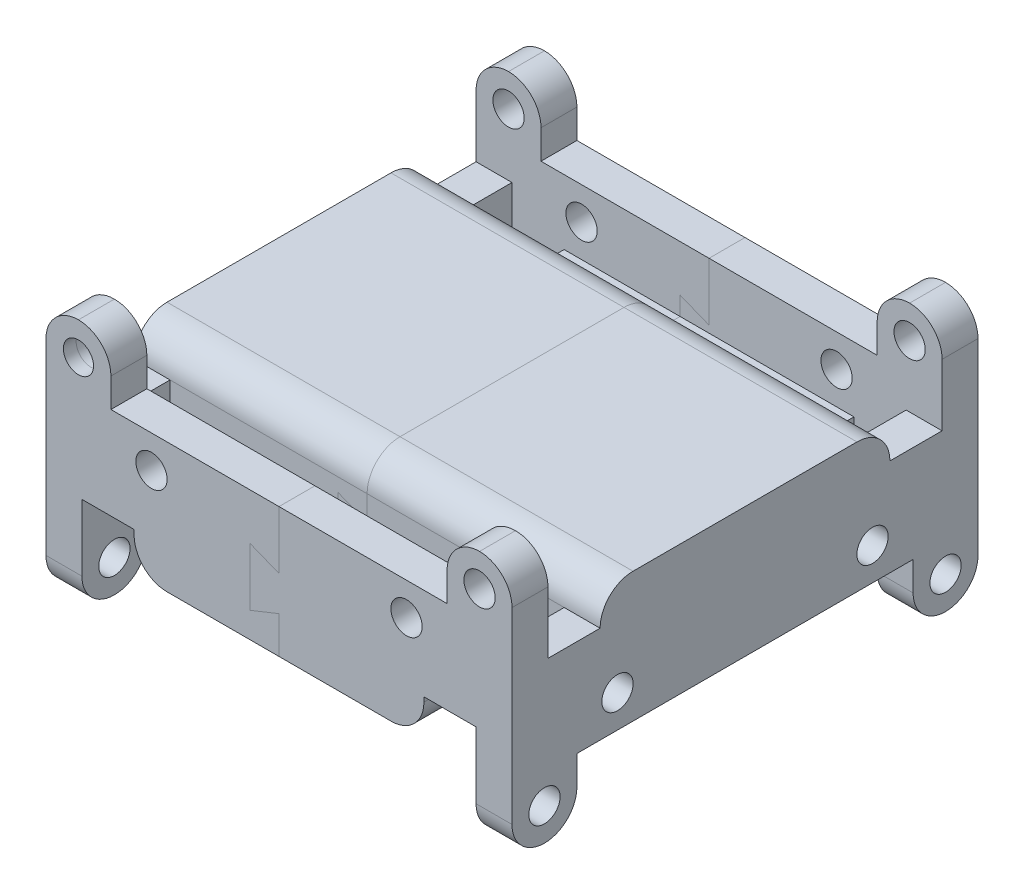
SolidWorks part; units mm, degrees
ref_plane "Plano frontal" through (0, 0, 0) normal (0, 0, 1) x (1, 0, 0)
ref_plane "Plano superior" through (0, 0, 0) normal (0, 1, 0) x (1, 0, 0)
ref_plane "Plano direito" through (0, 0, 0) normal (1, 0, 0) x (0, 0, -1)
sketch "Esboço1" plane through (0, 0, 0) normal (0, 0, 1) x (1, 0, 0)
  line L0 (0, 0) -> (5.6, 0)
  line L1 (0, 0) -> (0, -11.45)
  line L2 (0, -11.45) -> (40.2, -11.45)
  line L3 (40.2, -11.45) -> (40.2, 0)
  line L4 (40.2, 0) -> (34.6, 0)
  line L5 (5.6, 0) -> (5.6, -5.85)
  line L6 (5.6, -5.85) -> (34.6, -5.85)
  line L7 (34.6, -5.85) -> (34.6, 0)
  circle A0 centre (2.8, -3.35) radius 1.35
  circle A1 centre (37.4, -3.35) radius 1.35
  circle A3 centre (31.1, -8.65) radius 1.35
  circle A4 centre (9.1, -8.65) radius 1.35
  dimension "D6" = 2.7
  dimension "D7" = 3.35
  dimension "D8" = 2.7
  dimension "D9" = 2.8
  dimension "D10" = 2.8
  dimension "D11" = 2.7
  dimension "D12" = 2.7
  dimension "D13" = 3.5
  dimension "D14" = 3.5
  dimension "D15" = 2.8
  dimension "D16" = 2.8
  dimension "D17" = 3.35
  dimension "D1" = 5.6
  dimension "D2" = 11.45
  dimension "D3" = 40.2
  dimension "D4" = 5.6
  dimension "D5" = 5.85
extrude "Ressalto-extrusão1" add sketch "Esboço1" along normal blind 2
sketch "Esboço3" plane through (0, -11.45, 0) normal (0, -1, 0) x (1, 0, 0)
  line L1 (0, 0) -> (40.2, 0)
  line L2 (0, 0) -> (0, 2)
  line L3 (0, 2) -> (40.2, 2)
  line L4 (40.2, 0) -> (40.2, 2)
extrude "Ressalto-extrusão2" add sketch "Esboço3" along normal blind 10.08
sketch "Esboço4" plane through (0, 0, 0) normal (0, 0, -1) x (-1, 0, 0)
  line L0 (0, 0) -> (0, -21.53) construction
  line L1 (-40.2, -21.53) -> (-37.1, -21.53)
  line L2 (-40.2, -21.53) -> (-40.2, -8.69)
  line L3 (-40.2, -8.69) -> (-37.1, -8.69)
  line L4 (-37.1, -21.53) -> (-37.1, -8.69)
  line L5 (0, -8.69) -> (-3.1, -8.69)
  line L6 (0, -8.69) -> (0, -21.53)
  line L7 (0, -21.53) -> (-3.1, -21.53)
  line L8 (-3.1, -8.69) -> (-3.1, -21.53)
  line L9 (0, -21.53) -> (-40.2, -21.53) construction
  dimension "D1" = 12.84
  dimension "D2" = 3.1
  dimension "D3" = 3.1
  dimension "D4" = 12.84
extrude "Ressalto-extrusão3" add sketch "Esboço4" along normal blind 34
sketch "Esboço5" plane through (37.1, 0, 0) normal (-1, 0, 0) x (0, 0, 1)
  line L0 (0, -21.53) -> (0, -8.69) construction
  line L2 (-34, -21.53) -> (0, -21.53) construction
  line L4 (-34, -21.53) -> (-34, -8.69) construction
  circle A0 centre (-6, -14.25) radius 1.35
  circle A2 centre (-28, -14.25) radius 1.35
  dimension "D1" = 2.7
  dimension "D2" = 2.7
  dimension "D3" = 6
  dimension "D4" = 7.28
  dimension "D5" = 7.28
  dimension "D6" = 6
extrude "Corte-extrusão1" cut sketch "Esboço5" against normal through all both and the other way through all
sketch "Esboço7" plane through (0, 0, 0) normal (0, 0, -1) x (-1, 0, 0)
  line L0 (0, 0) -> (0, -8.69) construction
  line L1 (-37.1, -21.53) -> (0, -21.53)
  line L2 (-37.1, -21.53) -> (-37.1, -18.29)
  line L3 (-37.1, -18.29) -> (0, -18.29)
  line L4 (0, -21.53) -> (0, -18.29)
  dimension "D1" = 3.24
extrude "Corte-extrusão2" cut sketch "Esboço7" against normal blind 2
sketch "Esboço12" plane through (0, 0, -34) normal (0, 0, -1) x (-1, 0, 0)
  line L0 (-5.6, 0) -> (0, 0)
  line L1 (-40.2, 0) -> (-34.6, 0)
  line L2 (-40.2, 0) -> (-40.2, -18.29)
  line L3 (-40.2, -18.29) -> (0, -18.29)
  line L4 (0, 0) -> (0, -18.29)
  line L6 (-34.6, 0) -> (-34.6, -5.85)
  line L7 (-34.6, -5.85) -> (-5.6, -5.85)
  line L8 (-5.6, 0) -> (-5.6, -5.85)
  circle A1 centre (-31.1, -8.65) radius 1.35
  circle A2 centre (-9.1, -8.65) radius 1.35
  circle A3 centre (-2.8, -3.35) radius 1.35
  circle A4 centre (-37.4, -3.35) radius 1.35
extrude "Ressalto-extrusão5" add sketch "Esboço12" along normal blind 2
sketch "Esboço18" plane through (0, 0, 0) normal (0, 0, 1) x (1, 0, 0)
  line L0 (3.1, -18.29) -> (3.1, -21.53) construction
  line L1 (0, -18.29) -> (3.1, -18.29)
  line L2 (0, -18.29) -> (0, -21.53)
  line L3 (0, -21.53) -> (3.1, -21.53)
  line L4 (3.1, -18.29) -> (3.1, -21.53)
extrude "Ressalto-extrusão6" add sketch "Esboço18" along normal blind 2
sketch "Esboço19" plane through (0, 0, -34) normal (0, 0, -1) x (-1, 0, 0)
  line L0 (0, -21.53) -> (0, -18.29) construction
  line L1 (-3.1, -21.53) -> (0, -21.53)
  line L2 (-3.1, -21.53) -> (-3.1, -18.29)
  line L3 (-3.1, -18.29) -> (0, -18.29)
  line L4 (0, -21.53) -> (0, -18.29)
  line L6 (-40.2, -21.53) -> (-37.1, -21.53)
  line L7 (-40.2, -21.53) -> (-40.2, -18.29)
  line L8 (-40.2, -18.29) -> (-37.1, -18.29)
  line L9 (-37.1, -21.53) -> (-37.1, -18.29)
extrude "Ressalto-extrusão7" add sketch "Esboço19" along normal blind 2
sketch "Esboço21" plane through (0, 0, 2) normal (0, 0, 1) x (1, 0, 0)
  line L0 (37.1, -21.53) -> (40.2, -21.53)
  line L1 (0, 0) -> (5.6, 0)
  line L2 (0, 0) -> (0, -21.53)
  line L3 (0, -21.53) -> (3.1, -21.53)
  line L4 (40.2, 0) -> (40.2, -21.53)
  line L6 (5.6, 0) -> (5.6, -5.85)
  line L7 (5.6, -5.85) -> (34.6, -5.85)
  line L8 (34.6, 0) -> (34.6, -5.85)
  line L9 (3.1, -18.29) -> (37.1, -18.29)
  line L10 (3.1, -18.29) -> (3.1, -21.53)
  line L12 (37.1, -18.29) -> (37.1, -21.53)
  line L13 (34.6, 0) -> (40.2, 0)
  circle A0 centre (2.8, -3.35) radius 1.3018
  circle A1 centre (9.1, -8.65) radius 1.35
  circle A2 centre (31.1, -8.65) radius 1.35
  circle A3 centre (37.4, -3.35) radius 1.35
extrude "Ressalto-extrusão8" add sketch "Esboço21" along normal blind 1.1
sketch "Esboço22" plane through (0, 0, -36) normal (0, 0, -1) x (-1, 0, 0)
  line L0 (-5.6, 0) -> (0, 0)
  line L1 (-40.2, 0) -> (-34.6, 0)
  line L2 (-40.2, 0) -> (-40.2, -21.53)
  line L3 (-40.2, -21.53) -> (-37.1, -21.53)
  line L4 (0, 0) -> (0, -21.53)
  line L6 (-37.1, -21.53) -> (-37.1, -18.29)
  line L7 (-37.1, -18.29) -> (-3.1, -18.29)
  line L8 (-3.1, -21.53) -> (-3.1, -18.29)
  line L9 (-34.6, -5.85) -> (-5.6, -5.85)
  line L10 (-34.6, -5.85) -> (-34.6, 0)
  line L12 (-5.6, -5.85) -> (-5.6, 0)
  line L13 (-3.1, -21.53) -> (0, -21.53)
  circle A0 centre (-37.4, -3.35) radius 1.35
  circle A1 centre (-31.1, -8.65) radius 1.35
  circle A2 centre (-9.1, -8.65) radius 1.35
  circle A3 centre (-2.8, -3.35) radius 1.35
extrude "Ressalto-extrusão9" add sketch "Esboço22" along normal blind 1.1
sketch "Esboço23" plane through (0, -21.53, 0) normal (0, -1, 0) x (1, 0, 0)
  line L0 (3.1, -37.1) -> (3.1, 3.1) construction
  line L1 (0, 3.1) -> (3.1, 3.1)
  line L2 (0, 3.1) -> (0, -2.5)
  line L3 (0, -2.5) -> (3.1, -2.5)
  line L4 (3.1, 3.1) -> (3.1, -2.5)
  line L5 (40.2, -37.1) -> (40.2, 3.1) construction
  line L6 (0, -37.1) -> (3.1, -37.1)
  line L7 (0, -37.1) -> (0, -31.5)
  line L8 (0, -31.5) -> (3.1, -31.5)
  line L9 (3.1, -37.1) -> (3.1, -31.5)
  line L10 (37.1, -37.1) -> (40.2, -37.1)
  line L11 (37.1, -37.1) -> (37.1, -31.5)
  line L12 (37.1, -31.5) -> (40.2, -31.5)
  line L13 (40.2, -37.1) -> (40.2, -31.5)
  line L15 (37.1, 3.1) -> (40.2, 3.1)
  line L16 (37.1, 3.1) -> (37.1, -2.5)
  line L17 (37.1, -2.5) -> (40.2, -2.5)
  line L18 (40.2, 3.1) -> (40.2, -2.5)
  dimension "D1" = 5.6
  dimension "D2" = 5.6
  dimension "D3" = 5.6
  dimension "D4" = 5.6
extrude "Ressalto-extrusão10" add sketch "Esboço23" along normal blind 5.85
sketch "Esboço24" plane through (0, 0, 0) normal (-1, 0, 0) x (0, 0, 1)
  line L1 (-31.5, -27.38) -> (-31.5, -21.53) construction
  line L2 (3.1, 0) -> (3.1, -27.38) construction
  line L3 (3.1, -27.38) -> (-2.5, -27.38) construction
  line L4 (-31.5, -27.38) -> (-37.1, -27.38) construction
  circle A0 centre (-34.3, -19.55) radius 1.35
  circle A1 centre (0.3, -19.55) radius 1.35
  point P10 (0.3, -27.38)
  dimension "D1" = 2.7
  dimension "D2" = 2.7
  dimension "D3" = 2.8
  dimension "D4" = 2.8
  dimension "D5" = 7.83
  dimension "D6" = 7.83
extrude "Corte-extrusão3" cut sketch "Esboço24" against normal up to surface (40.2 mm away) up to face at (40.2, -14.25, -4.65)
sketch "Esboço25" plane through (0, -18.29, 0) normal (0, -1, 0) x (1, 0, 0)
  line L6 (3.1, -37.1) -> (7.6, -37.1)
  line L7 (3.1, -37.1) -> (3.1, -34)
  line L8 (3.1, -34) -> (7.6, -34)
  line L9 (37.1, -37.1) -> (37.1, -34)
  line L10 (32.6, 3.1) -> (37.1, 3.1)
  line L11 (3.1, 3.1) -> (7.6, 3.1)
  line L16 (3.1, 3.1) -> (3.1, 0)
  line L17 (3.1, 0) -> (7.6, 0)
  line L18 (37.1, 3.1) -> (37.1, 0)
  line L22 (7.6, 3.1) -> (7.6, 0)
  line L25 (37.1, 0) -> (32.6, 0)
  line L26 (32.6, 3.1) -> (32.6, 0)
  line L28 (32.6, -34) -> (37.1, -34)
  line L32 (7.6, -34) -> (7.6, -37.1)
  line L33 (37.1, -37.1) -> (32.6, -37.1)
  line L36 (32.6, -37.1) -> (32.6, -34)
  dimension "D1" = 4.5
  dimension "D2" = 4.5
  dimension "D3" = 4.5
  dimension "D4" = 4.5
sketch "Esboço27" plane through (0, -21.53, 0) normal (0, -1, 0) x (1, 0, 0)
  line L28 (0, -2.5) -> (3.1, -2.5)
  line L29 (0, -2.5) -> (0, -31.5)
  line L30 (0, -31.5) -> (3.1, -31.5)
  line L31 (3.1, -2.5) -> (3.1, -31.5)
  line L32 (40.2, -2.5) -> (37.1, -2.5)
  line L33 (40.2, -2.5) -> (40.2, -31.5)
  line L34 (40.2, -31.5) -> (37.1, -31.5)
  line L35 (37.1, -2.5) -> (37.1, -31.5)
extrude "Corte-extrusão6" cut sketch "Esboço25" against normal blind 4.48
extrude "Corte-extrusão7" cut sketch "Esboço27" against normal blind 4.48
sketch "Esboço28" plane through (0, -18.29, 0) normal (0, -1, 0) x (1, 0, 0)
  line L1 (7.6, 3.1) -> (32.6, 3.1)
  line L2 (7.6, 3.1) -> (7.6, -37.1)
  line L3 (7.6, -37.1) -> (32.6, -37.1)
  line L4 (32.6, 3.1) -> (32.6, -37.1)
extrude "Corte-extrusão8" cut sketch "Esboço28" against normal blind 1.24
sketch "Esboço29" plane through (0, 0, -34) normal (0, 0, 1) x (1, 0, 0)
  line L1 (7.6, -17.05) -> (32.6, -17.05)
  line L2 (7.6, -17.05) -> (7.6, -11.45)
  line L3 (7.6, -11.45) -> (32.6, -11.45)
  line L4 (32.6, -17.05) -> (32.6, -11.45)
  dimension "D1" = 25
  dimension "D2" = 5.6
extrude "Ressalto-extrusão11" add sketch "Esboço29" along normal up to surface (34 mm away) up to face at (32.45, -8.65, 0)
sketch "Esboço31" plane through (0, -8.69, 0) normal (0, 1, 0) x (1, 0, 0)
  line L40 (0, 34) -> (0, 0) construction
  line L49 (0, 29.5) -> (3.1, 29.5)
  line L50 (0, 29.5) -> (0, 4.5)
  line L51 (0, 4.5) -> (3.1, 4.5)
  line L52 (3.1, 29.5) -> (3.1, 4.5)
  line L53 (3.1, 34) -> (3.1, 0) construction
  line L54 (37.1, 34) -> (37.1, 0) construction
  line L55 (37.1, 29.5) -> (40.2, 29.5)
  line L56 (37.1, 29.5) -> (37.1, 4.5)
  line L57 (37.1, 4.5) -> (40.2, 4.5)
  line L58 (40.2, 29.5) -> (40.2, 4.5)
  line L59 (40.2, 34) -> (40.2, 0) construction
  line L60 (0, 34) -> (3.1, 34) construction
  line L62 (40.2, 0) -> (34.6, 0) construction
  line L63 (34.6, 34) -> (40.2, 34) construction
  dimension "D1" = 25
  dimension "D2" = 4.5
  dimension "D3" = 4.5
  dimension "D4" = 4.5
extrude "Ressalto-extrusão12" add sketch "Esboço31" along normal blind 2.84
sketch "Esboço32" plane through (37.1, 0, 0) normal (-1, 0, 0) x (0, 0, 1)
  line L1 (-29.5, -5.85) -> (-4.5, -5.85)
  line L2 (-29.5, -5.85) -> (-29.5, -11.45)
  line L3 (-29.5, -11.45) -> (-4.5, -11.45)
  line L4 (-4.5, -5.85) -> (-4.5, -11.45)
  dimension "D1" = 25
  dimension "D2" = 5.6
extrude "Ressalto-extrusão13" add sketch "Esboço32" along normal up to surface (34 mm away) up to face at (3.1, -15.3325, -17)
fillet "Filete1" radius 2.84 4 edges at (32.6, -17.05, -17) (7.6, -17.05, -17) (20.1, -5.85, -29.5) (20.1, -5.85, -4.5)
sketch "Esboço33" plane through (0, 0, 0) normal (0, 1, 0) x (1, 0, 0)
  line L1 (0, 37.1) -> (5.6, 37.1)
  line L2 (0, 37.1) -> (0, 34)
  line L3 (0, 34) -> (5.6, 34)
  line L4 (5.6, 37.1) -> (5.6, 34)
  line L5 (34.6, 34) -> (40.2, 34)
  line L6 (34.6, 34) -> (34.6, 37.1)
  line L7 (34.6, 37.1) -> (40.2, 37.1)
  line L8 (40.2, 34) -> (40.2, 37.1)
  line L9 (40.2, -3.1) -> (34.6, -3.1)
  line L10 (40.2, -3.1) -> (40.2, 0)
  line L11 (40.2, 0) -> (34.6, 0)
  line L12 (34.6, -3.1) -> (34.6, 0)
  line L13 (5.6, -3.1) -> (0, -3.1)
  line L14 (5.6, -3.1) -> (5.6, 0)
  line L15 (5.6, 0) -> (0, 0)
  line L16 (0, -3.1) -> (0, 0)
extrude "Corte-extrusão9" cut sketch "Esboço33" against normal blind 0.55
sketch "Esboço35" plane through (0, -27.38, 0) normal (0, -1, 0) x (1, 0, 0)
  line L1 (0, -2.5) -> (3.1, -2.5)
  line L2 (0, -2.5) -> (0, 3.1)
  line L3 (0, 3.1) -> (3.1, 3.1)
  line L4 (3.1, -2.5) -> (3.1, 3.1)
  line L5 (37.1, -2.5) -> (40.2, -2.5)
  line L6 (37.1, -2.5) -> (37.1, 3.1)
  line L7 (37.1, 3.1) -> (40.2, 3.1)
  line L8 (40.2, -2.5) -> (40.2, 3.1)
  line L9 (40.2, -37.1) -> (37.1, -37.1)
  line L10 (40.2, -37.1) -> (40.2, -31.5)
  line L11 (40.2, -31.5) -> (37.1, -31.5)
  line L12 (37.1, -37.1) -> (37.1, -31.5)
  line L13 (3.1, -37.1) -> (0, -37.1)
  line L14 (3.1, -37.1) -> (3.1, -31.5)
  line L15 (3.1, -31.5) -> (0, -31.5)
  line L16 (0, -37.1) -> (0, -31.5)
extrude "Corte-extrusão10" cut sketch "Esboço35" against normal blind 5.03
fillet "Filete2" radius 2.8 16 edges at (34.6, -0.55, 1.55) (40.2, -0.55, 1.55) (0, -0.55, 1.55) (5.6, -0.55, 1.55) (40.2, -0.55, -35.55) (34.6, -0.55, -35.55) (5.6, -0.55, -35.55) (0, -0.55, -35.55) (1.55, -22.35, -31.5) (1.55, -22.35, -37.1) (38.65, -22.35, -37.1) (38.65, -22.35, -31.5) (38.65, -22.35, 3.1) (38.65, -22.35, -2.5) (1.55, -22.35, -2.5) (1.55, -22.35, 3.1)
sketch "Esboço36" plane through (0, 0, 3.1) normal (0, 0, 1) x (1, 0, 0)
  line L0 (17.6, -9.85) -> (17.6, -14.85)
  line L1 (0, -3.35) -> (0, -19.55) construction
  line L5 (20.1, -0.55) -> (20.1, -10.85)
  line L6 (20.1, -13.85) -> (20.1, -22.35)
  line L11 (17.6, -9.85) -> (20.1, -10.85)
  line L13 (17.6, -14.85) -> (20.1, -13.85)
  dimension "D1" = 21.8
  dimension "D2" = 68.199
  dimension "D3" = 68.199
  dimension "D4" = 8.5
  dimension "D5" = 10.3
  dimension "D9" = 2.5
  dimension "D10" = 20.1
  dimension "D11" = 20.1
split "Dividir1" trim tools "Esboço36" bodies to split 139 resulting bodies 140 141
